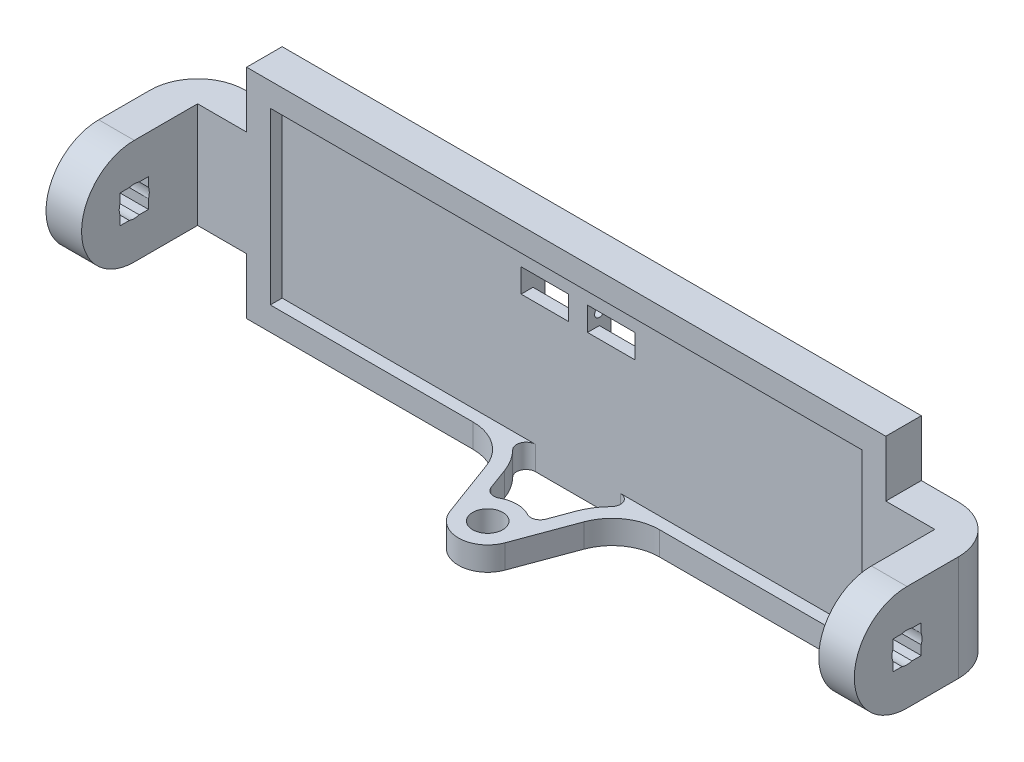
SolidWorks part; units mm, degrees
ref_plane "Front Plane" through (0, 0, 0) normal (0, 0, 1) x (1, 0, 0)
ref_plane "Top Plane" through (0, 0, 0) normal (0, 1, 0) x (1, 0, 0)
ref_plane "Right Plane" through (0, 0, 0) normal (1, 0, 0) x (0, 0, -1)
sketch "Sketch1" plane through (0, 0, 0) normal (0, 0, 1) x (1, 0, 0)
  line L0 (-62.415, 17.965) -> (62.415, 17.965)
  line L1 (-61.915, 17.465) -> (61.915, 17.465) construction
  line L2 (-61.915, 17.465) -> (-61.915, -17.465) construction
  line L3 (-61.915, -17.465) -> (61.915, -17.465) construction
  line L4 (61.915, 17.465) -> (61.915, -17.465) construction
  line L5 (-61.915, 17.465) -> (61.915, -17.465) construction
  line L6 (-61.915, -17.465) -> (61.915, 17.465) construction
  line L7 (62.415, 17.965) -> (62.415, -17.965)
  line L8 (-62.415, -17.965) -> (62.415, -17.965)
  line L9 (-62.415, 17.965) -> (-62.415, -17.965)
  line L10 (-67.415, 22.965) -> (67.415, 22.965)
  line L11 (67.415, 22.965) -> (67.415, -22.965)
  line L12 (-67.415, -22.965) -> (67.415, -22.965)
  line L13 (-67.415, 22.965) -> (-67.415, -22.965)
  point P0 (0, 0)
  dimension "D2" = 34.93
  dimension "D1" = 123.83
  dimension "D3" = 0.5
  dimension "D4" = 5
extrude "Boss-Extrude1" add sketch "Sketch1" along normal mid plane 5 contours L10 L13 L12 L11 L9 L0 L7 L8 | L0 L9 L8 L7 | L0 L7 L8 L9 | L10 L11 L12 L13 region at (0, 0, 0) region at (0, 21.5406, 0)
extrude "Boss-Extrude2" add sketch "Sketch1<3>" along normal mid plane 5 from surface starting at face at (0, 0, 2.5)
sketch "Sketch1<3>" plane through (0, 0, 0) normal (0, 0, 1) x (1, 0, 0) same geometry as "Sketch1"
sketch "Sketch2" plane through (0, -22.965, 0) normal (0, -1, 0) x (1, 0, 0)
  line L0 (-67.415, 2.5) -> (67.415, 2.5) construction
  line L1 (-67.415, 5) -> (-67.415, -2.5) construction
  line L2 (67.415, 5) -> (67.415, -2.5) construction
  line L5 (67.415, 5) -> (-67.415, 5) construction
  line L7 (0, 2.5) -> (0, 21.55) construction
  line L8 (-5.7921, 23.6907) -> (-12.7, 5)
  line L9 (-12.7, 5) -> (12.7, 5)
  line L10 (5.7921, 23.6907) -> (12.7, 5)
  circle A0 centre (0, 21.55) radius 3.175
  circle A1 centre (0, 21.55) radius 6.175
  point P18 (0, 5)
  line M10 (67.415, 5) -> (-67.415, 5)
  dimension "D3" = 6.35
  dimension "D1" = 2.5
  dimension "D2" = 19.05
  dimension "D5" = 12.7
  dimension "D4" = 3
extrude "Boss-Extrude3" add sketch "Sketch2" against normal up to surface (5 mm away) contours A1 L8 L10 M10 | A1 A0 region at (0, -22.965, 10.9171) region at (0, -22.965, 27.5503) up to face at (0, -17.965, 3.75)
fillet "Fillet1" radius 10 2 edges at (-12.7, -20.465, 5) (12.7, -20.465, 5)
sketch "Sketch5" plane through (0, 0, -2.5) normal (0, 0, -1) x (-1, 0, 0)
  line L0 (0, 22.965) -> (0, -22.965) construction
  line L1 (67.415, 22.965) -> (-67.415, 22.965) construction
  line L2 (67.415, -22.965) -> (-67.415, -22.965) construction
  line L3 (12, 7.965) -> (2, 7.965)
  line L4 (-12, 12.965) -> (-2, 12.965)
  line L5 (-12, 12.965) -> (-12, 7.965)
  line L6 (-12, 7.965) -> (-2, 7.965)
  line L7 (-2, 12.965) -> (-2, 7.965)
  line L8 (-12, 12.965) -> (-2, 7.965) construction
  line L9 (-12, 7.965) -> (-2, 12.965) construction
  line L10 (2, 12.965) -> (2, 7.965)
  line L11 (12, 12.965) -> (2, 12.965)
  line L12 (12, 12.965) -> (12, 7.965)
  point P6 (-7, 10.465)
  dimension "D1" = 5
  dimension "D2" = 10
  dimension "D3" = 2
  dimension "D4" = 10
extrude "Cut-Extrude4" cut sketch "Sketch5" against normal through all both and the other way through all
sketch "Sketch6" plane through (-2, 0, 0) normal (-1, 0, 0) x (0, 0, 1)
  line L0 (2.5, 12.965) -> (-2.5, 7.965) construction
  line L4 (-2.5, 7.965) -> (2.5, 7.965)
  line L5 (2.5, 7.965) -> (2.5, 12.965)
  line L6 (2.5, 12.965) -> (-2.5, 12.965)
  line L7 (-2.5, 12.965) -> (-2.5, 7.965)
  line L8 (-2.5, 7.965) -> (2.5, 7.965) construction
  line L9 (2.5, 7.965) -> (2.5, 12.965) construction
  line L10 (2.5, 12.965) -> (-2.5, 12.965) construction
  line L11 (-2.5, 12.965) -> (-2.5, 7.965) construction
  circle A0 centre (0, 10.465) radius 1
  dimension "D2" = 2
  dimension "D1" = 0
extrude "Cut-Extrude5" cut sketch "Sketch6" against normal up to next from surface starting at face at (-2, 10.465, 0)
sketch "Sketch7" plane through (0, 0, -2.5) normal (0, 0, -1) x (-1, 0, 0)
  line L0 (0, 22.965) -> (0, 0) construction
  line L1 (-85.25, 11.115) -> (-77.75, 11.115)
  line L2 (-85.25, 11.115) -> (-85.25, -11.115)
  line L3 (-85.25, -11.115) -> (-77.75, -11.115)
  line L4 (-77.75, 11.115) -> (-77.75, -11.115)
  line L5 (-85.25, 11.115) -> (-77.75, -11.115) construction
  line L6 (-85.25, -11.115) -> (-77.75, 11.115) construction
  line L7 (67.415, 22.965) -> (-67.415, 22.965) construction
  line L8 (0, 0) -> (-67.415, 0) construction
  line L9 (-67.415, 22.965) -> (-67.415, -22.965) construction
  line L10 (-77.75, 11.115) -> (-67.415, 11.115)
  line L11 (-67.415, 11.115) -> (-67.415, -11.115)
  line L12 (-67.415, -11.115) -> (-77.75, -11.115)
  line L13 (67.415, -11.115) -> (77.75, -11.115)
  line L14 (67.415, 11.115) -> (67.415, -11.115)
  line L15 (77.75, 11.115) -> (67.415, 11.115)
  line L16 (85.25, -11.115) -> (77.75, -11.115)
  line L17 (77.75, 11.115) -> (77.75, -11.115)
  line L18 (85.25, 11.115) -> (77.75, 11.115)
  line L19 (85.25, 11.115) -> (85.25, -11.115)
  point P0 (-81.5, 0)
  line M16 (-67.415, 22.965) -> (-67.415, -22.965)
  line M18 (67.415, -22.965) -> (67.415, 22.965)
  dimension "D2" = 7.5
  dimension "D3" = 22.23
  dimension "D1" = 170.5
extrude "Boss-Extrude4" add sketch "Sketch7" against normal up to surface (7.5 mm away) contours L12 L10 L4 M16 | L4 L1 L2 L3 | L19 L18 L17 L16 | L17 L15 L13 M18 region at (81.5, 0, -2.5) region at (72.5825, 0, -2.5) region at (-72.5825, 0, -2.5) region at (-81.5, 0, -2.5) up to face at (0, -6.8217, 5)
extrude "Boss-Extrude5" add sketch "Sketch7<4>" against normal blind 25.4 from surface contours L4 L1 L2 L3 | L19 L18 L17 L16 region at (81.5, 0, -2.5) region at (-81.5, 0, -2.5) starting at face at (0, -4.093, 5)
sketch "Sketch7<4>" plane through (0, 0, -2.5) normal (0, 0, -1) x (-1, 0, 0) same geometry as "Sketch7"
sketch "Sketch10" plane through (0, 0, 0) normal (1, 0, 0) x (0, 0, -1)
  line L0 (-2.5, 17.965) -> (-2.5, -17.965) construction
  line L1 (-2.5, 17.965) -> (-2.5, -17.965) construction
  line L2 (-18.36, 0) -> (-15.185, 0) construction
  line L3 (2.5, 11.115) -> (2.5, -11.115) construction
  line L4 (-30.4, -11.115) -> (2.5, -11.115) construction
  line L5 (-18.36, 11.115) -> (-30.4, 11.115)
  line L6 (-30.4, 11.115) -> (-30.4, -11.115)
  line L7 (-30.4, -11.115) -> (-18.36, -11.115)
  line L8 (-15.185, 0) -> (-7.245, 0) construction
  line L9 (-7.245, 0) -> (2.5, 0) construction
  circle A0 centre (-18.36, 0) radius 3.175
  arc A1 (-18.36, 11.115) -> (-18.36, -11.115) centre (-18.36, 0) ccw
  arc A2 (-7.245, 0) -> (-18.36, 11.115) centre (-18.36, 0) ccw construction
  arc A3 (-18.36, -11.115) -> (-7.245, 0) centre (-18.36, 0) ccw construction
  dimension "D1" = 6.35
  dimension "D2" = 20.86
extrude "Cut-Extrude7" cut sketch "Sketch10" against normal through all both and the other way through all
sketch "Sketch11" plane through (0, -22.965, 0) normal (0, -1, 0) x (1, 0, 0)
  line L0 (-4.8142, 17.6829) -> (-7.4714, 10.4933)
  line L1 (7.4714, 10.4933) -> (4.8142, 17.6829)
  line L3 (-2.9781, 22.6507) -> (-4.8142, 17.6829) construction
  line L4 (-2.9781, 22.6507) -> (-7.4714, 10.4933) construction
  line L5 (4.8142, 17.6829) -> (2.9781, 22.6507) construction
  line L6 (7.4714, 10.4933) -> (2.9781, 22.6507) construction
  line L7 (-62.415, 2.5) -> (62.415, 2.5) construction
  line L8 (-16.0945, 2.5) -> (16.0945, 2.5)
  line L9 (-62.415, 2.5) -> (-16.0945, 2.5) construction
  line L10 (16.0945, 2.5) -> (62.415, 2.5) construction
  line L11 (-67.415, -2.5) -> (67.415, -2.5) construction
  line L24 (-67.415, -2.5) -> (67.415, -2.5)
  line L25 (67.415, -2.5) -> (67.415, 5)
  line L26 (67.415, 5) -> (19.6652, 5)
  line L27 (10.2854, 11.5333) -> (5.7921, 23.6907)
  line L28 (-5.7921, 23.6907) -> (-10.2854, 11.5333)
  line L29 (-19.6652, 5) -> (-67.415, 5)
  line L30 (-67.415, 5) -> (-67.415, -2.5)
  line L31 (-67.415, -2.5) -> (67.415, -2.5) construction
  line L32 (67.415, -2.5) -> (67.415, 5) construction
  line L33 (67.415, 5) -> (19.6652, 5) construction
  line L34 (10.2854, 11.5333) -> (5.7921, 23.6907) construction
  line L35 (-5.7921, 23.6907) -> (-10.2854, 11.5333) construction
  line L36 (-19.6652, 5) -> (-67.415, 5) construction
  line L37 (-67.415, 5) -> (-67.415, -2.5) construction
  arc A0 (-16.0945, 2.5) -> (-7.4714, 10.4933) centre (-19.6652, 15) ccw
  arc A1 (4.8142, 17.6829) -> (-4.8142, 17.6829) centre (0, 21.55) ccw construction
  arc A2 (7.4714, 10.4933) -> (16.0945, 2.5) centre (19.6652, 15) ccw
  arc A3 (10.2854, 11.5333) -> (19.6652, 5) centre (19.6652, 15) ccw
  arc A4 (5.7921, 23.6907) -> (-5.7921, 23.6907) centre (0, 21.55) ccw
  arc A5 (-19.6652, 5) -> (-10.2854, 11.5333) centre (-19.6652, 15) ccw
  arc A6 (10.2854, 11.5333) -> (19.6652, 5) centre (19.6652, 15) ccw construction
  arc A7 (5.7921, 23.6907) -> (-5.7921, 23.6907) centre (0, 21.55) ccw construction
  arc A8 (-19.6652, 5) -> (-10.2854, 11.5333) centre (-19.6652, 15) ccw construction
  arc A9 (16.0945, 2.5) -> (19.6652, 2) centre (19.6652, 15) ccw construction
  arc A10 (7.4714, 10.4933) -> (19.6652, 2) centre (19.6652, 15) ccw construction
  circle A11 centre (0, 21.55) radius 6.175
  arc A12 (-4.8142, 17.6829) -> (4.8142, 17.6829) centre (0, 21.55) ccw
  arc A13 (-19.6652, 2) -> (-16.0945, 2.5) centre (-19.6652, 15) ccw construction
  arc A14 (-19.6652, 2) -> (-7.4714, 10.4933) centre (-19.6652, 15) ccw construction
  dimension "D1" = 0
  dimension "D2" = 3
  dimension "D3" = 3
extrude "Cut-Extrude8" cut sketch "Sketch11" against normal up to next
fillet "Fillet2" radius 2 4 edges at (16.0945, -20.465, 2.5) (4.8142, -20.465, 17.6829) (-4.8142, -20.465, 17.6829) (-16.0945, -20.465, 2.5)
fillet "Fillet5" radius 10 2 edges at (-85.25, 0, -2.5) (85.25, 0, -2.5)
sketch "Sketch12" plane through (0, 0, 2.5) normal (0, 0, 1) x (1, 0, 0)
  line L0 (0, 17.965) -> (0, -17.965) construction
  line L1 (-57.415, 12.965) -> (-17, 12.965)
  line L2 (-57.415, 12.965) -> (-57.415, -12.965)
  line L3 (-57.415, -12.965) -> (-17, -12.965)
  line L4 (-17, 12.965) -> (-17, -12.965)
  line L5 (-62.415, 17.965) -> (62.415, 17.965) construction
  line L6 (5.7921, -17.965) -> (-5.7921, -17.965) construction
  line L8 (-37.2075, 12.965) -> (-37.2075, 17.965) construction
  line L9 (-57.415, 0) -> (-62.415, 0) construction
  line L10 (-62.415, -17.965) -> (-62.415, 17.965) construction
  line L11 (-37.2075, -12.965) -> (-37.2075, -17.965) construction
  line L12 (-19.6652, -17.965) -> (-62.415, -17.965) construction
  line L13 (-12, 10.465) -> (-17, 10.465) construction
  line L14 (-12, 12.965) -> (-12, 7.965) construction
  line L15 (57.415, -12.965) -> (17, -12.965)
  line L16 (17, 12.965) -> (17, -12.965)
  line L17 (57.415, 12.965) -> (17, 12.965)
  line L18 (57.415, 12.965) -> (57.415, -12.965)
  dimension "D1" = 5
chamfer "Chamfer3" distance 2.5 angle 45 4 edges at (7, 12.965, -2.5) (7, 7.965, -2.5) (-7, 12.965, -2.5) (-7, 7.965, -2.5)
sketch "Sketch13" plane through (0, 0, 0) normal (1, 0, 0) x (0, 0, -1)
  line L0 (-18.36, 3.175) -> (-18.36, -3.175) construction
  line L2 (-21.36, 3) -> (-15.36, 3)
  line L3 (-21.36, 3) -> (-21.36, -3)
  line L4 (-21.36, -3) -> (-15.36, -3)
  line L5 (-15.36, 3) -> (-15.36, -3)
  line L6 (-21.36, 3) -> (-15.36, -3) construction
  line L7 (-21.36, -3) -> (-15.36, 3) construction
  circle A0 centre (-18.36, 0) radius 3.175 construction
  point P5 (-18.36, 0)
  dimension "D1" = 6
extrude "Cut-Extrude9" cut sketch "Sketch13" against normal through all both and the other way through all
equation "\"CamWidth\"= 123.83"
equation "\"CamHeight\"= 34.93"
equation "\"D2@Sketch1\"=\"CamHeight\""
equation "\"D1@Sketch1\"=\"CamWidth\""
equation "\"CamWraparound\"= 5"
equation "\"CamOffset\"= 0.5"
equation "\"D3@Sketch1\"=\"CamOffset\""
equation "\"Face2Face\"= 15.16mm"
equation "\"ArmThickness\"= 7.5mm"
equation "\"D2@Sketch7\"=\"ArmThickness\""
equation "\"Pivot2Pivot\"= 170.5mm"
equation "\"D1@Sketch7\"=\"Pivot2Pivot\""
